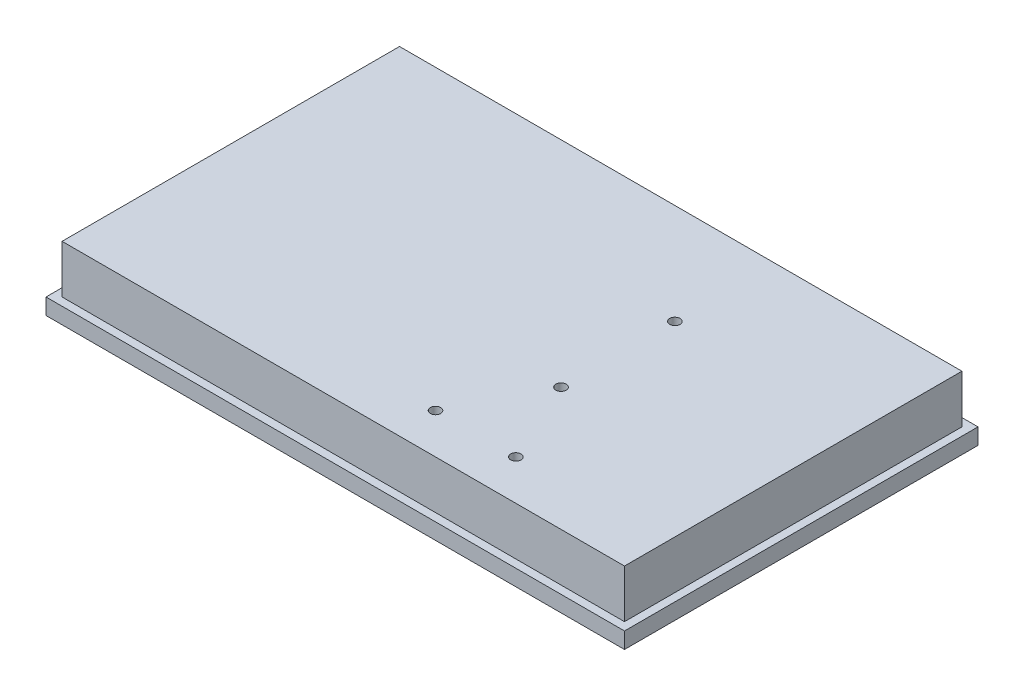
SolidWorks part; units mm, degrees
material "Gray Cast Iron"
ref_plane "Front Plane" through (0, 0, 0) normal (0, 0, 1) x (1, 0, 0)
ref_plane "Top Plane" through (0, 0, 0) normal (0, 1, 0) x (1, 0, 0)
ref_plane "Right Plane" through (0, 0, 0) normal (1, 0, 0) x (0, 0, -1)
sketch "Sketch1" plane through (0, 0, 0) normal (0, 1, 0) x (1, 0, 0)
  line L0 (-228.6, -139.7) -> (228.6, -139.7)
  line L1 (228.6, -139.7) -> (228.6, 139.7)
  line L2 (228.6, 139.7) -> (-228.6, 139.7)
  line L3 (-228.6, 139.7) -> (-228.6, -139.7)
extrude "Boss-Extrude1" add sketch "Sketch1" along normal blind 12.7
sketch "Sketch2" plane through (0, 0, 0) normal (0, 1, 0) x (1, 0, 0)
  line L0 (-222.25, -133.35) -> (222.25, -133.35)
  line L1 (222.25, -133.35) -> (222.25, 133.35)
  line L2 (222.25, 133.35) -> (-222.25, 133.35)
  line L3 (-222.25, 133.35) -> (-222.25, -133.35)
extrude "Boss-Extrude2" add sketch "Sketch2" along normal blind 38.1 from offset 12.7
sketch "Sketch3" plane through (0, 0, 0) normal (0, 1, 0) x (1, 0, 0)
  circle A0 centre (74.75, 54) radius 4.1
  circle A1 centre (74.75, -36) radius 4.1
  circle A2 centre (41.15, -101.6) radius 4.1
  circle A3 centre (104.65, -101.6) radius 4.1
  dimension "D1" = 8.2
  dimension "D2" = 8.2
  dimension "D3" = 8.2
  dimension "D4" = 8.2
extrude "Cut-Extrude1" cut sketch "Sketch3" against normal mid plane 152.4
sketch "Sketch4" plane through (0, 0, 0) normal (0, 1, 0) x (1, 0, 0)
  circle A0 centre (41.15, -101.6) radius 7.5
  circle A1 centre (104.65, -101.6) radius 7.5
  dimension "D1" = 15
  dimension "D2" = 15
extrude "Cut-Extrude2" cut sketch "Sketch4" against normal mid plane 9
